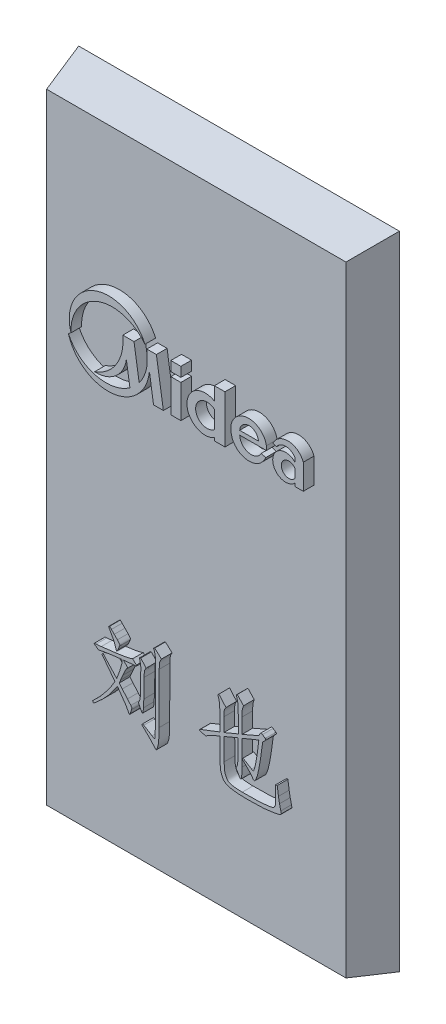
SolidWorks part; units mm, degrees
ref_plane "前视基准面" through (0, 0, 0) normal (0, 0, 1) x (1, 0, 0)
ref_plane "上视基准面" through (0, 0, 0) normal (0, 1, 0) x (1, 0, 0)
ref_plane "右视基准面" through (0, 0, 0) normal (1, 0, 0) x (0, 0, -1)
other "Configuration Table"
sketch "草图1" plane through (0, 0, 0) normal (0, 0, 1) x (1, 0, 0)
  line L18 (-15, -30) -> (15, -30)
  line L19 (-15, -30) -> (-15, 30)
  line L20 (-15, 30) -> (15, 30)
  line L21 (15, -30) -> (15, 30)
  line L22 (-15, -30) -> (15, 30) construction
  line L23 (-15, 30) -> (15, -30) construction
  point P0 (0, 0)
  dimension "D2" = 60
  dimension "D1" = 30
ref_plane "基准面1" through (0, 0, 4) normal (0, 0, 1) x (1, 0, 0)
sketch "草图2" plane through (0, 0, 4) normal (0, 0, 1) x (1, 0, 0)
  line L0 (-15, 30) -> (15, 30) construction
  line L1 (-14, -29) -> (14, -29)
  line L2 (-14, -29) -> (-14, 29)
  line L3 (-14, 29) -> (14, 29)
  line L4 (14, -29) -> (14, 29)
  line L5 (-14, -29) -> (14, 29) construction
  line L6 (-14, 29) -> (14, -29) construction
  line L7 (15, -30) -> (15, 30) construction
  point P0 (0, 0)
  dimension "D1" = 1
  dimension "D2" = 1
loft "放样1" add profiles "草图1", "草图2" connector at (-15, -30, 0) connector at (-14, -29, 4)
sketch "草图4" plane through (0, 0, 4) normal (0, 0, 1) x (1, 0, 0)
  line L6 (-14, -17) -> (14, -17) construction
  line L7 (-14, -29) -> (-14, 29) construction
  line L8 (14, -29) -> (14, 29) construction
  text T0 "刘也" font "汉仪长仿宋体" height 6
  dimension "D1" = 17
extrude "凸台-拉伸3" add sketch "草图4" along normal blind 1
sketch "草图5" plane through (0, 0, 0) normal (0, 0, -1) x (-1, 0, 0)
  line L4 (0, 18) -> (0, 0) construction
  line L5 (0, 0) -> (0, -18) construction
  line L6 (15, -30) -> (-15, -30) construction
  circle A7 centre (0, 0) radius 5.5
  circle A8 centre (0, 18) radius 5.5
  circle A9 centre (0, -18) radius 5.5
  dimension "D1" = 11
  dimension "D2" = 12
extrude "切除-拉伸1" cut sketch "草图5" against normal blind 2
sketch "草图7" plane through (0, 0, 4) normal (0, 0, 1) x (1, 0, 0)
  line L0 (3.2108, -13.9623) -> (1.3838, -14.6693) construction
  line L1 (1.3838, -14.8163) -> (1.8889, -14.9544) construction
  line L2 (3.2223, -14.2896) -> (3.2338, -16.284) construction
  line L3 (8.9065, -17.5088) -> (8.7864, -16.9911) construction
  line L4 (8.7864, -16.9911) -> (8.6892, -16.4387) construction
  line L5 (8.6892, -16.4387) -> (8.569, -15.6192) construction
  line L6 (8.569, -15.6192) -> (8.4258, -15.6358) construction
  line L7 (8.4258, -15.6358) -> (8.413, -17.2071) construction
  line L8 (3.6072, -16.1882) -> (3.5944, -14.1349) construction
  line L9 (3.5944, -14.1349) -> (4.9163, -13.5826) construction
  line L10 (4.9163, -13.5826) -> (4.9163, -14.7997) construction
  line L11 (4.832, -16.3186) -> (4.9892, -16.6024) construction
  line L12 (5.2654, -15.7918) -> (5.2654, -13.4445) construction
  line L13 (5.2654, -13.4445) -> (6.8507, -12.7976) construction
  line L14 (6.1782, -15.4901) -> (5.3728, -14.9979) construction
  line L15 (5.3728, -14.9979) -> (5.3012, -15.127) construction
  line L16 (5.3012, -15.127) -> (5.6131, -15.4211) construction
  line L17 (5.6131, -15.4211) -> (5.9737, -15.7918) construction
  line L18 (5.9737, -15.7918) -> (6.2984, -16.1971) construction
  line L19 (7.4401, -12.3744) -> (7.1882, -12.1839) construction
  line L20 (7.0195, -12.1583) -> (6.8277, -12.4524) construction
  line L21 (6.8277, -12.4524) -> (5.2769, -13.1249) construction
  line L22 (5.2769, -13.1249) -> (5.2769, -11.7185) construction
  line L23 (5.4214, -10.7341) -> (4.832, -10.1127) construction
  line L24 (4.832, -10.1127) -> (4.7361, -10.1997) construction
  line L25 (4.9291, -11.753) -> (4.9291, -13.2629) construction
  line L26 (4.9291, -13.2629) -> (3.5829, -13.8242) construction
  line L27 (3.5829, -13.8242) -> (3.5829, -12.547) construction
  line L28 (3.7746, -11.7006) -> (3.1149, -10.9412) construction
  line L29 (3.1149, -10.9412) -> (3.0178, -11.0447) construction
  line L30 (3.2108, -12.3744) -> (3.2108, -13.9623) construction
  line L31 (-2.8861, -10.2163) -> (-2.9948, -10.2853) construction
  line L32 (-2.8017, -11.5459) -> (-2.826, -16.4822) construction
  line L33 (-3.138, -17.4488) -> (-3.9076, -16.9744) construction
  line L34 (-3.9076, -16.9744) -> (-4.0035, -16.9054) construction
  line L35 (-4.0035, -16.9054) -> (-4.0994, -17.0089) construction
  line L36 (-4.0994, -17.0089) -> (-3.9677, -17.1547) construction
  line L37 (-3.9677, -17.1547) -> (-3.3553, -17.7505) construction
  line L38 (-3.3553, -17.7505) -> (-2.9219, -18.2248) construction
  line L39 (-2.4898, -16.4643) -> (-2.4655, -11.7185) construction
  line L40 (-2.2609, -10.7954) -> (-2.8861, -10.2163) construction
  line L41 (-4.1838, -12.4434) -> (-4.1953, -12.8142) construction
  line L42 (-4.1953, -12.8142) -> (-4.2323, -14.6437) construction
  line L43 (-4.3525, -15.5323) -> (-4.2554, -15.7138) construction
  line L44 (-4.2554, -15.7138) -> (-4.148, -15.9209) construction
  line L45 (-3.9434, -15.5847) -> (-3.9076, -14.8598) construction
  line L46 (-3.9076, -14.8598) -> (-3.8718, -13.0814) construction
  line L47 (-3.6915, -12.2453) -> (-4.1953, -11.675) construction
  line L48 (-4.1953, -11.675) -> (-4.3154, -11.7275) construction
  line L49 (-8.702, -17.3887) -> (-8.6061, -17.5344) construction
  line L50 (-8.6061, -17.5344) -> (-8.4731, -17.4309) construction
  line L51 (-5.5658, -16.215) -> (-5.4214, -16.4822) construction
  line L52 (-5.4214, -16.4822) -> (-5.3255, -16.6638) construction
  line L53 (-5.1695, -16.6638) -> (-5.0608, -16.2917) construction
  line L54 (-5.1209, -15.9734) -> (-5.4341, -15.6103) construction
  line L55 (-5.4341, -15.6103) -> (-5.9264, -15.049) construction
  line L56 (-5.9264, -15.049) -> (-6.214, -14.7128) construction
  line L57 (-6.214, -14.7128) -> (-6.0823, -14.411) construction
  line L58 (-6.0823, -14.411) -> (-5.8535, -13.8932) construction
  line L59 (-5.4098, -13.0993) -> (-5.7934, -12.6505) construction
  line L60 (-5.7934, -12.6505) -> (-5.1938, -12.5905) construction
  line L61 (-5.1938, -12.5905) -> (-4.6287, -12.547) construction
  line L62 (-4.5929, -12.4434) -> (-4.9649, -12.1238) construction
  line L63 (-7.885, -12.5905) -> (-8.3657, -12.625) construction
  line L64 (-8.4859, -12.7452) -> (-8.2328, -12.9356) construction
  line L65 (-8.2328, -12.9356) -> (-8.1612, -12.9957) construction
  line L66 (-8.1612, -12.9957) -> (-7.9566, -12.9523) construction
  line L67 (-7.9566, -12.9523) -> (-7.4516, -12.8577) construction
  line L68 (-7.4516, -12.8577) -> (-6.9722, -12.7886) construction
  line L69 (-6.9722, -12.7886) -> (-5.9506, -12.6672) construction
  line L70 (-5.9506, -12.6672) -> (-5.9506, -12.8577) construction
  line L71 (-7.6447, -13.1594) -> (-7.729, -13.0737) construction
  line L72 (-7.729, -13.0737) -> (-7.8249, -13.1773) construction
  line L73 (-7.8249, -13.1773) -> (-7.729, -13.3064) construction
  line L74 (-8.6176, -17.3017) -> (-8.702, -17.3887) construction
  line L75 (-7.2113, -10.6305) -> (-7.1154, -10.7775) construction
  line L76 (-6.9722, -11.0537) -> (-6.8034, -11.3554) construction
  line L77 (-6.5273, -12.0292) -> (-6.503, -12.1149) construction
  line L78 (-6.3112, -12.0292) -> (-6.191, -11.7185) construction
  line L79 (-6.3828, -11.2953) -> (-6.6717, -10.9936) construction
  line L80 (-6.6717, -10.9936) -> (-6.9351, -10.7264) construction
  line L81 (-6.9351, -10.7264) -> (-7.1039, -10.5538) construction
  line L82 (-7.1039, -10.5538) -> (-7.2113, -10.6305) construction
  line L83 (3.2108, -13.9623) -> (1.3838, -14.6693)
  line L84 (1.3838, -14.8163) -> (1.8889, -14.9544)
  line L85 (3.2223, -14.2896) -> (3.2338, -16.284)
  line L86 (8.9065, -17.5088) -> (8.7864, -16.9911)
  line L87 (8.7864, -16.9911) -> (8.6892, -16.4387)
  line L88 (8.6892, -16.4387) -> (8.569, -15.6192)
  line L89 (8.569, -15.6192) -> (8.4258, -15.6358)
  line L90 (8.4258, -15.6358) -> (8.413, -17.2071)
  line L91 (3.6072, -16.1882) -> (3.5944, -14.1349)
  line L92 (3.5944, -14.1349) -> (4.9163, -13.5826)
  line L93 (4.9163, -13.5826) -> (4.9163, -14.7997)
  line L94 (4.832, -16.3186) -> (4.9892, -16.6024)
  line L95 (5.2654, -15.7918) -> (5.2654, -13.4445)
  line L96 (5.2654, -13.4445) -> (6.8507, -12.7976)
  line L97 (6.1782, -15.4901) -> (5.3728, -14.9979)
  line L98 (5.3728, -14.9979) -> (5.3012, -15.127)
  line L99 (5.3012, -15.127) -> (5.6131, -15.4211)
  line L100 (5.6131, -15.4211) -> (5.9737, -15.7918)
  line L101 (5.9737, -15.7918) -> (6.2984, -16.1971)
  line L102 (7.4401, -12.3744) -> (7.1882, -12.1839)
  line L103 (7.0195, -12.1583) -> (6.8277, -12.4524)
  line L104 (6.8277, -12.4524) -> (5.2769, -13.1249)
  line L105 (5.2769, -13.1249) -> (5.2769, -11.7185)
  line L106 (5.4214, -10.7341) -> (4.832, -10.1127)
  line L107 (4.832, -10.1127) -> (4.7361, -10.1997)
  line L108 (4.9291, -11.753) -> (4.9291, -13.2629)
  line L109 (4.9291, -13.2629) -> (3.5829, -13.8242)
  line L110 (3.5829, -13.8242) -> (3.5829, -12.547)
  line L111 (3.7746, -11.7006) -> (3.1149, -10.9412)
  line L112 (3.1149, -10.9412) -> (3.0178, -11.0447)
  line L113 (3.2108, -12.3744) -> (3.2108, -13.9623)
  line L114 (-2.8861, -10.2163) -> (-2.9948, -10.2853)
  line L115 (-2.8017, -11.5459) -> (-2.826, -16.4822)
  line L116 (-3.138, -17.4488) -> (-3.9076, -16.9744)
  line L117 (-3.9076, -16.9744) -> (-4.0035, -16.9054)
  line L118 (-4.0035, -16.9054) -> (-4.0994, -17.0089)
  line L119 (-4.0994, -17.0089) -> (-3.9677, -17.1547)
  line L120 (-3.9677, -17.1547) -> (-3.3553, -17.7505)
  line L121 (-3.3553, -17.7505) -> (-2.9219, -18.2248)
  line L122 (-2.4898, -16.4643) -> (-2.4655, -11.7185)
  line L123 (-2.2609, -10.7954) -> (-2.8861, -10.2163)
  line L124 (-4.1838, -12.4434) -> (-4.1953, -12.8142)
  line L125 (-4.1953, -12.8142) -> (-4.2323, -14.6437)
  line L126 (-4.3525, -15.5323) -> (-4.2554, -15.7138)
  line L127 (-4.2554, -15.7138) -> (-4.148, -15.9209)
  line L128 (-3.9434, -15.5847) -> (-3.9076, -14.8598)
  line L129 (-3.9076, -14.8598) -> (-3.8718, -13.0814)
  line L130 (-3.6915, -12.2453) -> (-4.1953, -11.675)
  line L131 (-4.1953, -11.675) -> (-4.3154, -11.7275)
  line L132 (-8.702, -17.3887) -> (-8.6061, -17.5344)
  line L133 (-8.6061, -17.5344) -> (-8.4731, -17.4309)
  line L134 (-5.5658, -16.215) -> (-5.4214, -16.4822)
  line L135 (-5.4214, -16.4822) -> (-5.3255, -16.6638)
  line L136 (-5.1695, -16.6638) -> (-5.0608, -16.2917)
  line L137 (-5.1209, -15.9734) -> (-5.4341, -15.6103)
  line L138 (-5.4341, -15.6103) -> (-5.9264, -15.049)
  line L139 (-5.9264, -15.049) -> (-6.214, -14.7128)
  line L140 (-6.214, -14.7128) -> (-6.0823, -14.411)
  line L141 (-6.0823, -14.411) -> (-5.8535, -13.8932)
  line L142 (-5.4098, -13.0993) -> (-5.7934, -12.6505)
  line L143 (-5.7934, -12.6505) -> (-5.1938, -12.5905)
  line L144 (-5.1938, -12.5905) -> (-4.6287, -12.547)
  line L145 (-4.5929, -12.4434) -> (-4.9649, -12.1238)
  line L146 (-7.885, -12.5905) -> (-8.3657, -12.625)
  line L147 (-8.4859, -12.7452) -> (-8.2328, -12.9356)
  line L148 (-8.2328, -12.9356) -> (-8.1612, -12.9957)
  line L149 (-8.1612, -12.9957) -> (-7.9566, -12.9523)
  line L150 (-7.9566, -12.9523) -> (-7.4516, -12.8577)
  line L151 (-7.4516, -12.8577) -> (-6.9722, -12.7886)
  line L152 (-6.9722, -12.7886) -> (-5.9506, -12.6672)
  line L153 (-5.9506, -12.6672) -> (-5.9506, -12.8577)
  line L154 (-7.6447, -13.1594) -> (-7.729, -13.0737)
  line L155 (-7.729, -13.0737) -> (-7.8249, -13.1773)
  line L156 (-7.8249, -13.1773) -> (-7.729, -13.3064)
  line L157 (-8.6176, -17.3017) -> (-8.702, -17.3887)
  line L158 (-7.2113, -10.6305) -> (-7.1154, -10.7775)
  line L159 (-6.9722, -11.0537) -> (-6.8034, -11.3554)
  line L160 (-6.5273, -12.0292) -> (-6.503, -12.1149)
  line L161 (-6.3112, -12.0292) -> (-6.191, -11.7185)
  line L162 (-6.3828, -11.2953) -> (-6.6717, -10.9936)
  line L163 (-6.6717, -10.9936) -> (-6.9351, -10.7264)
  line L164 (-6.9351, -10.7264) -> (-7.1039, -10.5538)
  line L165 (-7.1039, -10.5538) -> (-7.2113, -10.6305)
  spline S0 degree 3 poles (-1033.717, 1696.6076) (14.5849, -31.3392) (2.3796, -13.84) (1.322, -14.7057) (1.3032, -14.7272) (1.2978, -14.7519) (1.3028, -14.776) (1.3219, -14.7941) (2.4833, -15.4174) (10.8456, 3.4261) (-689.6183, -1891.6231) knots -16.626684 -16.626684 -16.626684 -16.626684 0.172084 0.308952 0.423314 0.521848 0.615174 0.717267 0.839241 17.04599 17.04599 17.04599 17.04599 only from (1.3838, -14.6693) to (1.3838, -14.8163) construction
  spline S1 degree 3 poles (-1193.4267, 1588.4483) (4.6942, -35.4098) (-2.0793, -17.6856) (2.0886, -14.8069) (2.1786, -14.7467) (2.255, -14.7057) (2.3236, -14.6723) (2.394, -14.6406) (2.4842, -14.6016) (2.5935, -14.5536) (2.723, -14.4991) (2.8716, -14.4348) (21.1798, -6.8784) (36.675, 7.0863) (846.5091, -1827.4773) knots -9.913111 -9.913111 -9.913111 -9.913111 0.088354 0.168711 0.240996 0.305231 0.342298 0.393919 0.460114 0.539323 0.633116 0.74183 0.864014 40.342075 40.342075 40.342075 40.342075 only from (1.8889, -14.9544) to (3.2223, -14.2896) construction
  spline S2 degree 3 poles (-1996.6425, -26.0924) (21.1619, -1.4114) (2.9373, -9.1514) (3.2408, -16.6481) (3.2493, -16.8011) (3.2608, -16.9395) (3.287, -17.0743) (3.3282, -17.2177) (3.3889, -17.3745) (3.4475, -17.514) (3.5093, -17.6275) (3.5725, -17.7068) (3.6497, -17.778) (3.7401, -17.842) (3.8439, -17.8993) (3.961, -17.9489) (4.091, -17.9913) (4.2346, -18.0246) (4.3907, -18.0542) (4.5598, -18.0774) (4.7413, -18.0999) (4.9353, -18.1162) (5.1417, -18.1268) (5.3603, -18.1366) (17.0583, -18.3013) (28.6468, -3.9526) (45.2697, -2017.6338) knots -5.726077 -5.726077 -5.726077 -5.726077 0.051298 0.096629 0.136668 0.171139 0.205044 0.243843 0.287585 0.336355 0.362012 0.388335 0.415202 0.443856 0.474721 0.507699 0.543092 0.581467 0.622821 0.667242 0.714879 0.765695 0.819407 0.876414 0.936712 9.962298 9.962298 9.962298 9.962298 only from (3.2338, -16.284) to (5.8305, -18.1391) construction
  spline S3 degree 3 poles (-13.558, -2017.9262) (-16.1126, -3.2156) (-4.8916, -18.3162) (6.2967, -18.1363) (6.5077, -18.135) (6.702, -18.1289) (6.8797, -18.1244) (7.0413, -18.1179) (7.1862, -18.1106) (7.3593, -18.0983) (7.5693, -18.079) (7.8251, -18.0454) (8.0919, -18.0098) (8.3171, -17.9718) (8.4924, -17.939) (8.6085, -17.9125) (8.7077, -17.8849) (8.7894, -17.8553) (8.8564, -17.8272) (8.9046, -17.795) (9.7801, -17.0547) (-10.3073, -3.2872) (1708.116, -1071.7951) knots -10.275083 -10.275083 -10.275083 -10.275083 0.076298 0.147407 0.213324 0.274064 0.329613 0.379985 0.425587 0.465631 0.542665 0.62318 0.707468 0.794943 0.837249 0.874555 0.906545 0.933712 0.95606 0.97423 0.988354 1.993762 1.993762 1.993762 1.993762 only from (5.8305, -18.1391) to (8.9538, -17.7249) construction
  spline S4 degree 3 poles (1950.4824, 462.1548) (-3.6389, -24.2841) (9.4886, -19.2587) (8.928, -17.6283) (8.3828, -15.5017) (24.8318, -10.629) (-1966.0478, -332.6785) knots -22.527171 -22.527171 -22.527171 -22.527171 0.152758 0.441236 0.761695 29.779876 29.779876 29.779876 29.779876 only from (8.9538, -17.7249) to (8.9065, -17.5088) construction
  spline S5 degree 3 poles (1964.363, -433.7342) (-12.5579, -7.9686) (9.2006, -15.0961) (8.374, -17.3632) (8.3303, -17.4427) (8.2869, -17.5147) (8.228, -17.5691) (8.157, -17.6037) (8.0635, -17.637) (7.9458, -17.6647) (7.8043, -17.6919) (7.6382, -17.714) (7.4476, -17.7331) (7.1586, -17.7525) (6.7742, -17.7729) (6.2972, -17.7876) (-12.0936, -18.089) (-30.4237, 1.2715) (-38.3924, -2017.04) knots -2.060584 -2.060584 -2.060584 -2.060584 0.022746 0.046909 0.073942 0.103777 0.121266 0.144564 0.173661 0.209707 0.252274 0.302159 0.35908 0.423101 0.560508 0.702361 0.848718 16.964876 16.964876 16.964876 16.964876 only from (8.413, -17.2071) to (5.3012, -17.7939) construction
  spline S6 degree 3 poles (-46.7827, -2016.9641) (22.8077, 5.2469) (13.3561, -18.3583) (4.7621, -17.7744) (4.5344, -17.7516) (4.3394, -17.7124) (4.1743, -17.6679) (4.0418, -17.6087) (3.9373, -17.5417) (3.8494, -17.4317) (3.7799, -17.2879) (3.7089, -17.1204) (3.6584, -16.9548) (3.628, -16.7397) (3.0291, -6.34) (22.0683, 4.4844) (-1996.1462, -34.556) knots -8.866171 -8.866171 -8.866171 -8.866171 0.102703 0.194721 0.275299 0.345385 0.405658 0.456275 0.49919 0.535795 0.603996 0.668093 0.728927 0.787086 0.898182 11.780137 11.780137 11.780137 11.780137 only from (5.3012, -17.7939) to (3.6072, -16.1882) construction
  spline S7 degree 3 poles (2004.3322, 28.2132) (-5.4357, 8.8885) (4.9939, -3.0766) (4.9157, -15.1159) (4.913, -15.2229) (4.9105, -15.3009) (4.9062, -15.3675) (4.8976, -15.4411) (4.8881, -15.5311) (4.8742, -15.6326) (4.8595, -15.7344) (4.8403, -15.8267) (4.8184, -15.904) (4.7924, -15.9663) (4.7664, -16.0149) (4.7485, -16.0553) (4.7377, -16.0864) (4.7267, -16.1124) (4.7369, -16.1442) (4.7545, -16.1874) (8.4419, -22.4311) (7.4888, -21.5343) (1094.0182, -1693.6924) knots -22.721442 -22.721442 -22.721442 -22.721442 0.117235 0.209236 0.277643 0.321637 0.358354 0.405016 0.463185 0.53135 0.600551 0.659631 0.71141 0.753745 0.788334 0.81677 0.837638 0.852065 0.86867 0.898605 0.942334 14.623876 14.623876 14.623876 14.623876 only from (4.9163, -14.7997) to (4.832, -16.3186) construction
  spline S8 degree 3 poles (-1550.7197, -1273.4139) (19.3456, 2.9931) (3.2309, -14.1918) (5.0799, -16.7505) (5.7712, -17.6613) (19.4263, 1.9782) (-1061.0354, -1708.7198) knots -34.275912 -34.275912 -34.275912 -34.275912 0.381659 0.667499 0.869536 12.383747 12.383747 12.383747 12.383747 only from (4.9892, -16.6024) to (5.1567, -16.8095) construction
  spline S9 degree 3 poles (918.7555, -1795.635) (-5.5243, 1.4675) (4.8071, -17.3305) (5.1958, -16.7827) (5.2129, -16.7483) (5.2282, -16.7063) (5.2394, -16.6557) (5.2459, -16.5944) (5.2522, -16.5121) (5.257, -16.4089) (5.2608, -16.2845) (5.2627, -16.1391) (5.4392, -7.5851) (-9.7444, 1.0472) (2005.1553, -7.1429) knots -1.687714 -1.687714 -1.687714 -1.687714 0.017456 0.042472 0.079552 0.130072 0.168818 0.227795 0.306061 0.404936 0.523255 0.662264 0.820778 24.999128 24.999128 24.999128 24.999128 only from (5.1567, -16.8095) to (5.2654, -15.7918) construction
  spline S10 degree 3 poles (1999.4433, -182.4933) (-0.9536, 17.1275) (8.3501, 1.4035) (6.8086, -13.2123) (6.7917, -13.371) (6.7732, -13.5025) (6.7549, -13.6268) (6.7362, -13.7638) (6.7125, -13.9226) (6.6791, -14.1669) (6.6279, -14.4944) (6.5596, -14.8224) (6.5056, -15.0718) (6.4665, -15.2245) (6.4351, -15.3421) (6.405, -15.4266) (6.3778, -15.4844) (6.3562, -15.5253) (6.3378, -15.5519) (6.3166, -15.5656) (6.2921, -15.5599) (6.2639, -15.5443) (4.0424, -14.2877) (11.2127, 0.4883) (-1139.8748, -1654.3969) knots -14.529546 -14.529546 -14.529546 -14.529546 0.077669 0.143357 0.196643 0.237586 0.276416 0.322552 0.376056 0.437289 0.569617 0.708128 0.772877 0.82528 0.866104 0.894742 0.914992 0.930089 0.941025 0.94733 0.953792 0.964678 0.979985 3.500837 3.500837 3.500837 3.500837 only from (6.8507, -12.7976) to (6.1782, -15.4901) construction
  spline S11 degree 3 poles (-1459.7871, -1376.4789) (16.124, -1.0165) (4.8212, -14.6345) (6.361, -16.2729) (7.1105, -16.8641) (15.6434, 1.6427) (-747.2579, -1868.7131) knots -40.720986 -40.720986 -40.720986 -40.720986 0.346655 0.629517 0.83833 17.401909 17.401909 17.401909 17.401909 only from (6.2984, -16.1971) to (6.4186, -16.3007) construction
  spline S12 degree 3 poles (837.9651, -1835.1249) (-8.1419, 10.6055) (5.776, -17.2113) (6.5025, -16.2565) (6.528, -16.2095) (6.5563, -16.1512) (6.5901, -16.0734) (6.631, -15.9775) (6.6736, -15.8661) (6.7146, -15.7421) (6.7515, -15.6071) (6.7856, -15.4601) (6.8204, -15.2999) (6.8542, -15.124) (6.8917, -14.9328) (6.9306, -14.7215) (6.9732, -14.4828) (7.0122, -14.2083) (7.0571, -13.8958) (7.0902, -13.6158) (7.1179, -13.389) (7.1385, -13.2361) (7.1567, -13.1048) (7.1715, -12.9952) (7.1853, -12.9069) (7.1977, -12.8407) (7.2081, -12.7966) (7.217, -12.763) (7.2413, -12.7362) (7.2737, -12.7029) (7.3166, -12.6607) (7.3686, -12.617) (7.4169, -12.5708) (7.4586, -12.5329) (7.4821, -12.4989) (7.4993, -12.4634) (7.0362, -10.9223) (-17.6107, -31.0912) (1493.2118, 1326.3414) knots -0.749252 -0.749252 -0.749252 -0.749252 0.011116 0.024256 0.034759 0.050015 0.070334 0.09545 0.124469 0.15558 0.188759 0.224443 0.263394 0.305925 0.352459 0.40264 0.459525 0.525733 0.60077 0.685168 0.727217 0.76409 0.795449 0.821898 0.843179 0.859308 0.869947 0.875726 0.883767 0.895184 0.909185 0.926664 0.943691 0.957044 0.966676 0.973237 0.984469 2.007557 2.007557 2.007557 2.007557 only from (6.4186, -16.3007) to (7.4401, -12.3744) construction
  spline S13 degree 3 poles (902.0496, 1776.4099) (0.6886, -34.6242) (9.0767, -12.9356) (7.086, -12.1281) (6.1315, -12.1467) (19.65, -37.5566) (-984.4161, 1724.6464) knots -32.736634 -32.736634 -32.736634 -32.736634 0.367152 0.634154 0.821366 13.935133 13.935133 13.935133 13.935133 only from (7.1882, -12.1839) to (7.0195, -12.1583) construction
  spline S14 degree 3 poles (-1994.6009, 0.495) (23.7054, -26.4113) (4.9761, -18.7485) (5.2835, -11.3643) (5.2914, -11.232) (5.3038, -11.1262) (5.3257, -11.034) (5.3512, -10.9406) (6.9792, -5.8121) (22.7426, -5.6507) (-1877.5534, 663.1337) knots -21.608795 -21.608795 -21.608795 -21.608795 0.198899 0.364768 0.496393 0.59539 0.682927 0.77943 0.885076 16.774062 16.774062 16.774062 16.774062 only from (5.2769, -11.7185) to (5.4214, -10.7341) construction
  spline S15 degree 3 poles (1902.8334, 619.7227) (-16.1551, -6.6372) (3.4236, -5.5784) (4.816, -10.4468) (4.8463, -10.5591) (4.8758, -10.7012) (4.902, -10.8854) (4.9158, -11.0799) (4.9214, -11.254) (4.9279, -11.4048) (4.905, -22.6176) (16.3078, -33.5295) (-1993.4919, -88.7053) knots -9.399112 -9.399112 -9.399112 -9.399112 0.086759 0.167144 0.240968 0.308143 0.443474 0.594867 0.67934 0.775169 0.882309 22.030604 22.030604 22.030604 22.030604 only from (4.7361, -10.1997) to (4.9291, -11.753) construction
  spline S16 degree 3 poles (-1996.3066, -6.3279) (21.0986, -26.1786) (3.2376, -19.0978) (3.5925, -12.2086) (3.6071, -12.0674) (3.6279, -11.9648) (3.6579, -11.8939) (3.6875, -11.8361) (6.3076, -7.6291) (19.1276, -10.4641) (-1635.6374, 1133.6983) knots -22.753125 -22.753125 -22.753125 -22.753125 0.200316 0.389353 0.554689 0.680516 0.74126 0.814082 0.900083 17.48624 17.48624 17.48624 17.48624 only from (3.5829, -12.547) to (3.7746, -11.7006) construction
  spline S17 degree 3 poles (1903.9912, 610.2623) (-20.7158, -5.6325) (1.4769, -5.2348) (3.1267, -11.4022) (3.1599, -11.5753) (3.1876, -11.7958) (3.8456, -21.4883) (-18.235, -31.7664) (2002.9406, 15.7492) knots -13.754831 -13.754831 -13.754831 -13.754831 0.142454 0.27858 0.408689 0.533703 0.771853 21.965234 21.965234 21.965234 21.965234 only from (3.0178, -11.0447) to (3.2108, -12.3744) construction
  spline S18 degree 3 poles (1863.0803, 709.0915) (-22.3797, -4.1401) (-5.0305, -4.4694) (-2.8997, -10.5404) (-2.8683, -10.6465) (-2.844, -10.7698) (-2.829, -10.9212) (-2.8225, -11.0733) (-2.8168, -11.193) (-2.8154, -11.2703) (-2.8106, -11.3328) (-2.8079, -11.3968) (-2.5223, -14.669) (-19.2275, -18.627) (1995.8178, 61.3832) knots -14.7087 -14.7087 -14.7087 -14.7087 0.116167 0.216181 0.30306 0.374052 0.509134 0.657525 0.72919 0.788892 0.837713 0.875556 0.938334 8.497053 8.497053 8.497053 8.497053 only from (-2.9948, -10.2853) to (-2.8017, -11.5459) construction
  spline S19 degree 3 poles (1996.6884, -57.1725) (-15.54, -4.2723) (-2.5643, -10.6635) (-2.8326, -16.6987) (-2.8349, -16.7929) (-2.8368, -16.8769) (-2.8416, -16.9497) (-2.8431, -17.0124) (-2.8477, -17.0639) (-2.8518, -17.1377) (-2.8594, -17.2275) (-2.8586, -17.3285) (-2.6706, -19.1698) (-24.0229, -19.8512) (1993.9836, -127.1361) knots -18.086944 -18.086944 -18.086944 -18.086944 0.116901 0.223456 0.319585 0.404033 0.479451 0.541837 0.595221 0.636857 0.766948 0.869544 0.944906 6.362298 6.362298 6.362298 6.362298 only from (-2.826, -16.4822) to (-2.8618, -17.4654) construction
  spline S20 degree 3 poles (1920.7346, -564.8783) (-19.9028, -9.0246) (-2.2232, -15.9139) (-2.8844, -17.541) (-2.8944, -17.5636) (-2.9124, -17.5786) (-2.943, -17.5624) (-2.9871, -17.5419) (-7.9881, -14.4729) (-0.924, -15.4233) (-1899.5268, 617.8288) knots -13.418067 -13.418067 -13.418067 -13.418067 0.123946 0.216991 0.278308 0.31908 0.381479 0.515917 0.721003 45.525651 45.525651 45.525651 45.525651 only from (-2.8618, -17.4654) to (-3.138, -17.4488) construction
  spline S21 degree 3 poles (194.9213, -2008.3902) (-15.0275, 1.5883) (-8.4676, -12.6222) (-2.8057, -18.3428) (-2.0182, -19.0945) (7.0662, -6.6445) (-1066.911, -1711.4586) knots -97.933846 -97.933846 -97.933846 -97.933846 0.408799 0.710783 0.906834 13.513962 13.513962 13.513962 13.513962 only from (-2.9219, -18.2248) to (-2.7416, -18.3897) construction
  spline S22 degree 3 poles (1541.3019, -1289.3663) (-17.2182, -8.6749) (-3.0151, -19.2135) (-2.6957, -18.315) (-2.6594, -18.2339) (-2.6181, -18.1202) (-2.5776, -17.9866) (-2.5431, -17.8417) (-2.5239, -17.6904) (-2.5098, -17.4826) (-2.5022, -17.2234) (-2.497, -16.9689) (-2.4939, -16.7788) (-2.491, -16.6565) (-2.4063, -10.64) (-11.8864, -4.6267) (1997.4337, -6.5983) knots -1.306783 -1.306783 -1.306783 -1.306783 0.011073 0.038994 0.08476 0.148534 0.222584 0.297979 0.375406 0.454948 0.615659 0.771094 0.84328 0.905715 0.957736 10.02345 10.02345 10.02345 10.02345 only from (-2.7416, -18.3897) to (-2.4898, -16.4643) construction
  spline S23 degree 3 poles (-2002.0433, 23.4082) (17.2178, -26.8655) (-2.9385, -18.8244) (-2.4518, -11.3454) (-2.4395, -11.2317) (-2.4299, -11.1629) (-2.4183, -11.1079) (-2.4062, -11.0612) (-2.3851, -11.014) (-2.3537, -10.9557) (0.2121, -6.3458) (14.755, -8.7652) (-1720.7414, 1012.1287) knots -22.788299 -22.788299 -22.788299 -22.788299 0.226747 0.424712 0.510059 0.582424 0.640662 0.684729 0.732249 0.801029 0.890645 17.139984 17.139984 17.139984 17.139984 only from (-2.4655, -11.7185) to (-2.2609, -10.7954) construction
  spline S24 degree 3 poles (1924.5555, 516.4873) (-21.4595, -4.1063) (-5.6484, -6.1098) (-4.2553, -11.9618) (-4.2351, -12.066) (-4.2157, -12.1849) (-3.2666, -19.1695) (-14.338, -27.5253) (1984.5585, 198.7689) knots -24.265145 -24.265145 -24.265145 -24.265145 0.176124 0.336499 0.483023 0.612769 0.832275 29.485687 29.485687 29.485687 29.485687 only from (-4.3154, -11.7275) to (-4.1838, -12.4434) construction
  spline S25 degree 3 poles (1993.4071, -111.1275) (-26.4009, -2.323) (-3.6574, -9.2924) (-4.2529, -14.9872) (-4.2827, -15.1305) (-4.3269, -15.2317) (-4.3657, -15.2981) (-4.3838, -15.3404) (-4.396, -15.3739) (-4.4028, -15.4128) (-3.7015, -17.7808) (17.82, -6.713) (-1681.3534, -1105.1804) knots -18.0051 -18.0051 -18.0051 -18.0051 0.201752 0.379581 0.534025 0.67384 0.735013 0.783251 0.822556 0.850486 0.909807 8.568288 8.568288 8.568288 8.568288 only from (-4.2323, -14.6437) to (-4.3525, -15.5323) construction
  spline S26 degree 3 poles (-1512.9602, -1328.6343) (10.4966, 3.2816) (-5.5522, -14.0466) (-4.0797, -16.0348) (-4.0465, -16.064) (-4.0156, -16.055) (-4.0025, -16.0314) (-3.9917, -16.0026) (-3.9815, -15.9618) (-3.9734, -15.9091) (-3.9642, -15.8448) (-3.9571, -15.7684) (-3.4918, -10.72) (-16.7031, -4.6524) (1991.2791, -152.9923) knots -10.887367 -10.887367 -10.887367 -10.887367 0.121964 0.207693 0.260892 0.300142 0.329863 0.376288 0.436469 0.514652 0.611416 0.722891 0.853081 22.971798 22.971798 22.971798 22.971798 only from (-4.148, -15.9209) to (-3.9434, -15.5847) construction
  spline S27 degree 3 poles (1994.0865, -101.0049) (-13.6723, -29.9635) (-3.8891, -21.5767) (-3.8702, -12.858) (-3.866, -12.7715) (-3.86, -12.6843) (-3.8474, -12.597) (-3.8347, -12.516) (-3.8137, -12.4521) (-3.7836, -12.3943) (-1.8693, -9.0083) (15.3369, -14.8877) (-1709.4277, 1031.8458) knots -29.538415 -29.538415 -29.538415 -29.538415 0.141799 0.263135 0.361172 0.438866 0.562703 0.663904 0.719374 0.792594 0.886876 14.061788 14.061788 14.061788 14.061788 only from (-3.8718, -13.0814) to (-3.6915, -12.2453) construction
  spline S28 degree 3 poles (1264.9967, -1559.4891) (-31.5873, -12.0786) (-13.6284, -22.0641) (-8.1342, -17.1422) (-7.9369, -16.9598) (-7.7283, -16.7545) (-7.5206, -16.5461) (-7.3343, -16.3462) (-7.1732, -16.1672) (-7.0581, -16.0237) (-6.9736, -15.91) (-6.9052, -15.8183) (-6.8336, -15.7144) (-6.7531, -15.6022) (-6.67, -15.4779) (-6.5781, -15.3451) (2.1562, -2.044) (17.435, 6.7071) (-1628.834, 1154.0726) knots -6.726074 -6.726074 -6.726074 -6.726074 0.062764 0.136145 0.220514 0.315903 0.411855 0.497633 0.57328 0.638674 0.670791 0.706683 0.746446 0.789663 0.836764 0.887318 0.941766 15.825984 15.825984 15.825984 15.825984 only from (-8.4731, -17.4309) to (-6.3828, -15.049) construction
  spline S29 degree 3 poles (-1774.7239, -949.3367) (-0.7487, -7.6484) (-7.3553, -13.3952) (-6.347, -15.1129) (-6.313, -15.1624) (-6.2693, -15.2266) (-6.2164, -15.3059) (-6.1504, -15.3976) (-6.0752, -15.5038) (-5.9929, -15.6196) (-5.909, -15.7352) (-5.8309, -15.8422) (-5.7637, -15.9368) (-5.7051, -16.0177) (-5.6581, -16.0866) (-5.617, -16.1403) (-2.5499, -20.6038) (-3.1453, -27.2731) (1710.5712, 1010.7307) knots -4.10249 -4.10249 -4.10249 -4.10249 0.017268 0.047445 0.089524 0.143804 0.211032 0.29024 0.381658 0.485286 0.589437 0.682632 0.764344 0.833847 0.893123 0.939986 0.976096 12.299151 12.299151 12.299151 12.299151 only from (-6.3828, -15.049) to (-5.5658, -16.215) construction
  spline S30 degree 3 poles (-1652.1034, -1151.5707) (8.8374, -2.9824) (-6.3284, -15.4657) (-5.2823, -16.7295) (-5.2616, -16.749) (-5.239, -16.7551) (-5.2169, -16.7491) (-5.1987, -16.7299) (-4.4002, -15.3061) (-20.3074, -6.3517) (1819.6509, -834.9933) knots -19.315907 -19.315907 -19.315907 -19.315907 0.184014 0.329932 0.435758 0.52042 0.60011 0.698183 0.82936 20.217518 20.217518 20.217518 20.217518 only from (-5.3255, -16.6638) to (-5.1695, -16.6638) construction
  spline S31 degree 3 poles (1756.3388, -963.5015) (-15.7851, -19.7388) (-6.0338, -20.2901) (-5.0347, -16.1894) (-5.0317, -16.153) (-5.0297, -16.1236) (-5.0402, -16.096) (-5.057, -16.0623) (-7.8026, -12.1779) (-16.0197, -15.5805) (1187.0566, 1589.806) knots -35.897109 -35.897109 -35.897109 -35.897109 0.175028 0.3144 0.421741 0.491694 0.565052 0.672076 0.818098 41.504706 41.504706 41.504706 41.504706 only from (-5.0608, -16.2917) to (-5.1209, -15.9734) construction
  spline S32 degree 3 poles (-1844.512, 772.8216) (-1.9985, -31.3954) (-8.803, -20.3942) (-5.7663, -13.6971) (-5.7298, -13.6114) (-5.6969, -13.5363) (-5.6669, -13.4717) (-5.6414, -13.4167) (-5.62, -13.3716) (-5.5873, -13.3017) (-3.5534, -10.1993) (22.2359, -28.7518) (-1476.7841, 1341.5083) knots -23.688236 -23.688236 -23.688236 -23.688236 0.124711 0.237544 0.339212 0.428998 0.50564 0.571681 0.627122 0.668853 0.823736 12.607364 12.607364 12.607364 12.607364 only from (-5.8535, -13.8932) to (-5.4098, -13.0993) construction
  spline S33 degree 3 poles (1048.4675, -1712.7468) (-20.15, 9.6222) (-5.0308, -13.2656) (-4.5787, -12.5119) (-4.4352, -11.4786) (-31.1321, -16.4036) (1947.3773, 423.0108) knots -17.330031 -17.330031 -17.330031 -17.330031 0.228603 0.460739 0.719052 22.488112 22.488112 22.488112 22.488112 only from (-4.6287, -12.547) to (-4.5929, -12.4434) construction
  spline S34 degree 3 poles (617.1539, -1912.8033) (1.0615, 6.6518) (0.4277, -10.6214) (-5.2524, -12.2113) (-5.4248, -12.2495) (-5.6173, -12.2898) (-5.8305, -12.3277) (-6.0647, -12.3642) (-16.7545, -13.9589) (-29.7673, 2.3999) (227.2617, -1998.576) knots -10.40378 -10.40378 -10.40378 -10.40378 0.082838 0.177515 0.284544 0.402898 0.534005 0.677173 0.832565 20.129151 20.129151 20.129151 20.129151 only from (-4.9649, -12.1238) to (-6.5873, -12.4345) construction
  spline S35 degree 3 poles (298.0282, -1988.6784) (34.5431, 3.4816) (14.3568, -9.9504) (-7.256, -12.5157) (-26.2506, -14.8362) (-46.4544, -6.0355) (171.7781, -2004.1497) knots -49.192308 -49.192308 -49.192308 -49.192308 0.264132 0.518317 0.763645 44.186385 44.186385 44.186385 44.186385 only from (-6.5873, -12.4345) to (-7.885, -12.5905) construction
  spline S36 degree 3 poles (-1461.4057, 1361.6465) (11.9395, -25.8139) (-5.9466, -12.0262) (-8.5083, -12.6493) (-8.5576, -12.6619) (-8.5585, -12.6948) (-6.6522, -14.1057) (-12.4698, 0.822) (848.919, -1819.5851) knots -27.163084 -27.163084 -27.163084 -27.163084 0.274008 0.539418 0.638409 0.701183 0.813539 22.170768 22.170768 22.170768 22.170768 only from (-8.3657, -12.625) to (-8.4859, -12.7452) construction
  spline S37 degree 3 poles (1980.3886, -245.9002) (-25.6618, -4.0136) (-5.2924, -9.814) (-5.9842, -13.0963) (-6.0243, -13.2582) (-6.0787, -13.4503) (-6.1499, -13.6689) (-6.2318, -13.9123) (-11.99, -28.9406) (-30.0035, -38.8194) (1823.522, -820.849) knots -5.750981 -5.750981 -5.750981 -5.750981 0.058152 0.137295 0.236273 0.356767 0.494511 0.647688 0.816423 29.295179 29.295179 29.295179 29.295179 only from (-5.9506, -12.8577) to (-6.4429, -14.4545) construction
  spline S38 degree 3 poles (-1440.4806, -1408.4344) (12.2022, -13.7825) (-2.3288, -18.9321) (-6.635, -14.2521) (-6.7478, -14.1367) (-6.9051, -13.9638) (-7.1046, -13.7457) (-7.3024, -13.5363) (-7.4406, -13.3794) (-7.5273, -13.2883) (-11.1426, -9.2579) (-21.1289, -11.1301) (1455.1445, 1350.6897) knots -10.550678 -10.550678 -10.550678 -10.550678 0.072662 0.155077 0.246174 0.346541 0.551898 0.74801 0.835624 0.906789 0.961595 10.027963 10.027963 10.027963 10.027963 only from (-6.4429, -14.4545) to (-7.6447, -13.1594) construction
  spline S39 degree 3 poles (-1690.9874, -1093.1833) (3.3964, -3.003) (-8.5702, -12.3185) (-7.6792, -13.3782) (-7.6356, -13.4372) (-7.5827, -13.4978) (-7.5262, -13.5706) (-7.4574, -13.6543) (-7.3699, -13.7703) (-7.2605, -13.9156) (-7.1281, -14.0897) (-6.975, -14.2939) (4.9528, -30.4112) (25.9086, -39.6948) (-1573.915, -1256.6215) knots -2.148203 -2.148203 -2.148203 -2.148203 0.015763 0.043388 0.082758 0.134752 0.173579 0.232037 0.310356 0.408975 0.526794 0.664916 0.822376 33.019448 33.019448 33.019448 33.019448 only from (-7.729, -13.3064) to (-6.6116, -14.7818) construction
  spline S40 degree 3 poles (1720.3243, -1023.3234) (-16.1487, 18.5257) (-0.3829, -5.2401) (-7.063, -15.5177) (-7.2989, -15.8542) (-7.5036, -16.115) (-7.6664, -16.3087) (-7.7781, -16.444) (-7.8861, -16.5659) (-7.9856, -16.679) (-8.079, -16.7812) (-8.1654, -16.8734) (-8.2462, -16.9542) (-8.3206, -17.0243) (-8.3868, -17.0855) (-8.4452, -17.1383) (-8.4946, -17.184) (-8.5356, -17.2221) (-8.5675, -17.2534) (-8.5919, -17.2758) (-10.0031, -18.7121) (-13.9652, -17.5077) (1380.8721, -1455.6115) knots -10.967114 -10.967114 -10.967114 -10.967114 0.13677 0.268528 0.395276 0.51773 0.575816 0.629956 0.680367 0.726837 0.769636 0.808773 0.843982 0.87557 0.903536 0.927593 0.948568 0.965902 0.979597 0.98994 0.996647 2.846485 2.846485 2.846485 2.846485 only from (-6.6116, -14.7818) to (-8.6176, -17.3017) construction
  spline S41 degree 3 poles (-1863.6245, -754.3794) (4.4911, -3.082) (-7.7846, -9.5752) (-7.0741, -10.8691) (-4.3579, -16.0121) (12.1418, -14.6441) (-1809.0679, -878.3222) knots -13.550654 -13.550654 -13.550654 -13.550654 0.090846 0.287239 0.590215 56.191237 56.191237 56.191237 56.191237 only from (-7.1154, -10.7775) to (-6.9722, -11.0537) construction
  spline S42 degree 3 poles (1834.9168, 768.1255) (-43.4567, -10.4562) (24.5419, 1.0806) (-32.1871, -38.5399) (1852.1265, 726.1252) knots -30.614491 -30.614491 -30.614491 -30.614491 0.497436 31.719294 31.719294 31.719294 31.719294 only from (-6.8034, -11.3554) to (-6.5273, -12.0292) construction
  spline S43 degree 3 poles (-1865.1417, -750.4644) (10.0329, -1.5337) (-7.3015, -10.4965) (-6.4726, -12.1947) (-6.45, -12.2151) (-6.4207, -12.2124) (-6.395, -12.1889) (-6.3692, -12.1506) (-4.9295, -9.4946) (-20.1862, 0.6082) (1823.1195, -820.1308) knots -15.623058 -15.623058 -15.623058 -15.623058 0.147979 0.251119 0.323111 0.388004 0.477994 0.606878 0.779247 25.920813 25.920813 25.920813 25.920813 only from (-6.503, -12.1149) to (-6.3112, -12.0292) construction
  spline S44 degree 3 poles (-1912.8987, -615.0411) (10.2854, -11.3835) (-7.4086, -14.4578) (-6.1458, -11.6023) (-6.1514, -11.5735) (-6.1633, -11.5549) (-6.1798, -11.5283) (-6.2061, -11.4958) (-6.2388, -11.4549) (-6.28, -11.4078) (-12.3004, -4.7951) (-23.0878, -2.3486) (1486.2203, 1319.7709) knots -17.033327 -17.033327 -17.033327 -17.033327 0.164438 0.264555 0.289914 0.332187 0.391502 0.47307 0.575597 0.69724 0.838081 52.760377 52.760377 52.760377 52.760377 only from (-6.191, -11.7185) to (-6.3828, -11.2953) construction
  spline S45 degree 3 poles (1.3838, -14.6693) (1.3711, -14.6746) (1.3482, -14.6842) (1.322, -14.7057) (1.3032, -14.7272) (1.2978, -14.7519) (1.3028, -14.776) (1.3219, -14.7941) (1.3491, -14.8087) (1.3713, -14.8135) (1.3838, -14.8163) knots 0 0 0 0 0.172084 0.308952 0.423314 0.521848 0.615174 0.717267 0.839241 1 1 1 1
  spline S46 degree 3 poles (1.8889, -14.9544) (1.9235, -14.9272) (1.9897, -14.8752) (2.0886, -14.8069) (2.1786, -14.7467) (2.255, -14.7057) (2.3236, -14.6723) (2.394, -14.6406) (2.4842, -14.6016) (2.5935, -14.5536) (2.723, -14.4991) (2.8716, -14.4348) (3.0408, -14.365) (3.1597, -14.3156) (3.2223, -14.2896) knots 0 0 0 0 0.088354 0.168711 0.240996 0.305231 0.342298 0.393919 0.460114 0.539323 0.633116 0.74183 0.864014 1 1 1 1
  spline S47 degree 3 poles (3.2338, -16.284) (3.2338, -16.3497) (3.2337, -16.4733) (3.2408, -16.6481) (3.2493, -16.8011) (3.2608, -16.9395) (3.287, -17.0743) (3.3282, -17.2177) (3.3889, -17.3745) (3.4475, -17.514) (3.5093, -17.6275) (3.5725, -17.7068) (3.6497, -17.778) (3.7401, -17.842) (3.8439, -17.8993) (3.961, -17.9489) (4.091, -17.9913) (4.2346, -18.0246) (4.3907, -18.0542) (4.5598, -18.0774) (4.7413, -18.0999) (4.9353, -18.1162) (5.1417, -18.1268) (5.3603, -18.1366) (5.5914, -18.1398) (5.7495, -18.1394) (5.8305, -18.1391) knots 0 0 0 0 0.051298 0.096629 0.136668 0.171139 0.205044 0.243843 0.287585 0.336355 0.362012 0.388335 0.415202 0.443856 0.474721 0.507699 0.543092 0.581467 0.622821 0.667242 0.714879 0.765695 0.819407 0.876414 0.936712 1 1 1 1
  spline S48 degree 3 poles (5.8305, -18.1391) (5.9119, -18.1394) (6.0691, -18.1399) (6.2967, -18.1363) (6.5077, -18.135) (6.702, -18.1289) (6.8797, -18.1244) (7.0413, -18.1179) (7.1862, -18.1106) (7.3593, -18.0983) (7.5693, -18.079) (7.8251, -18.0454) (8.0919, -18.0098) (8.3171, -17.9718) (8.4924, -17.939) (8.6085, -17.9125) (8.7077, -17.8849) (8.7894, -17.8553) (8.8564, -17.8272) (8.9046, -17.795) (8.9417, -17.7637) (8.9501, -17.737) (8.9538, -17.7249) knots 0 0 0 0 0.076298 0.147407 0.213324 0.274064 0.329613 0.379985 0.425587 0.465631 0.542665 0.62318 0.707468 0.794943 0.837249 0.874555 0.906545 0.933712 0.95606 0.97423 0.988354 1 1 1 1
  spline S49 degree 3 poles (8.9538, -17.7249) (8.9519, -17.7138) (8.9463, -17.6816) (8.928, -17.6283) (8.9124, -17.5675) (8.9083, -17.5264) (8.9065, -17.5088) knots 0 0 0 0 0.152758 0.441236 0.761695 1 1 1 1
  spline S50 degree 3 poles (8.413, -17.2071) (8.4097, -17.2325) (8.4027, -17.2847) (8.374, -17.3632) (8.3303, -17.4427) (8.2869, -17.5147) (8.228, -17.5691) (8.157, -17.6037) (8.0635, -17.637) (7.9458, -17.6647) (7.8043, -17.6919) (7.6382, -17.714) (7.4476, -17.7331) (7.1586, -17.7525) (6.7742, -17.7729) (6.2972, -17.7876) (5.8045, -17.7956) (5.4708, -17.7945) (5.3012, -17.7939) knots 0 0 0 0 0.022746 0.046909 0.073942 0.103777 0.121266 0.144564 0.173661 0.209707 0.252274 0.302159 0.35908 0.423101 0.560508 0.702361 0.848718 1 1 1 1
  spline S51 degree 3 poles (5.3012, -17.7939) (5.2044, -17.7933) (5.0209, -17.792) (4.7621, -17.7744) (4.5344, -17.7516) (4.3394, -17.7124) (4.1743, -17.6679) (4.0418, -17.6087) (3.9373, -17.5417) (3.8494, -17.4317) (3.7799, -17.2879) (3.7089, -17.1204) (3.6584, -16.9548) (3.628, -16.7397) (3.6133, -16.4846) (3.6092, -16.2841) (3.6072, -16.1882) knots 0 0 0 0 0.102703 0.194721 0.275299 0.345385 0.405658 0.456275 0.49919 0.535795 0.603996 0.668093 0.728927 0.787086 0.898182 1 1 1 1
  spline S52 degree 3 poles (4.9163, -14.7997) (4.9164, -14.8611) (4.9166, -14.9706) (4.9157, -15.1159) (4.913, -15.2229) (4.9105, -15.3009) (4.9062, -15.3675) (4.8976, -15.4411) (4.8881, -15.5311) (4.8742, -15.6326) (4.8595, -15.7344) (4.8403, -15.8267) (4.8184, -15.904) (4.7924, -15.9663) (4.7664, -16.0149) (4.7485, -16.0553) (4.7377, -16.0864) (4.7267, -16.1124) (4.7369, -16.1442) (4.7545, -16.1874) (4.7897, -16.247) (4.8166, -16.2926) (4.832, -16.3186) knots 0 0 0 0 0.117235 0.209236 0.277643 0.321637 0.358354 0.405016 0.463185 0.53135 0.600551 0.659631 0.71141 0.753745 0.788334 0.81677 0.837638 0.852065 0.86867 0.898605 0.942334 1 1 1 1
  spline S53 degree 3 poles (4.9892, -16.6024) (5.0056, -16.6332) (5.0341, -16.6872) (5.0799, -16.7505) (5.1155, -16.7974) (5.1451, -16.8061) (5.1567, -16.8095) knots 0 0 0 0 0.381659 0.667499 0.869536 1 1 1 1
  spline S54 degree 3 poles (5.1567, -16.8095) (5.163, -16.8089) (5.1783, -16.8074) (5.1958, -16.7827) (5.2129, -16.7483) (5.2282, -16.7063) (5.2394, -16.6557) (5.2459, -16.5944) (5.2522, -16.5121) (5.257, -16.4089) (5.2608, -16.2845) (5.2627, -16.1391) (5.2662, -15.9725) (5.2657, -15.8545) (5.2654, -15.7918) knots 0 0 0 0 0.017456 0.042472 0.079552 0.130072 0.168818 0.227795 0.306061 0.404936 0.523255 0.662264 0.820778 1 1 1 1
  spline S55 degree 3 poles (6.8507, -12.7976) (6.8431, -12.8747) (6.8292, -13.0171) (6.8086, -13.2123) (6.7917, -13.371) (6.7732, -13.5025) (6.7549, -13.6268) (6.7362, -13.7638) (6.7125, -13.9226) (6.6791, -14.1669) (6.6279, -14.4944) (6.5596, -14.8224) (6.5056, -15.0718) (6.4665, -15.2245) (6.4351, -15.3421) (6.405, -15.4266) (6.3778, -15.4844) (6.3562, -15.5253) (6.3378, -15.5519) (6.3166, -15.5656) (6.2921, -15.5599) (6.2639, -15.5443) (6.2236, -15.5215) (6.1946, -15.5015) (6.1782, -15.4901) knots 0 0 0 0 0.077669 0.143357 0.196643 0.237586 0.276416 0.322552 0.376056 0.437289 0.569617 0.708128 0.772877 0.82528 0.866104 0.894742 0.914992 0.930089 0.941025 0.94733 0.953792 0.964678 0.979985 1 1 1 1
  spline S56 degree 3 poles (6.2984, -16.1971) (6.3096, -16.2123) (6.33, -16.2399) (6.361, -16.2729) (6.3897, -16.2956) (6.4098, -16.2991) (6.4186, -16.3007) knots 0 0 0 0 0.346655 0.629517 0.83833 1 1 1 1
  spline S57 degree 3 poles (6.4186, -16.3007) (6.4348, -16.3001) (6.4703, -16.2988) (6.5025, -16.2565) (6.528, -16.2095) (6.5563, -16.1512) (6.5901, -16.0734) (6.631, -15.9775) (6.6736, -15.8661) (6.7146, -15.7421) (6.7515, -15.6071) (6.7856, -15.4601) (6.8204, -15.2999) (6.8542, -15.124) (6.8917, -14.9328) (6.9306, -14.7215) (6.9732, -14.4828) (7.0122, -14.2083) (7.0571, -13.8958) (7.0902, -13.6158) (7.1179, -13.389) (7.1385, -13.2361) (7.1567, -13.1048) (7.1715, -12.9952) (7.1853, -12.9069) (7.1977, -12.8407) (7.2081, -12.7966) (7.217, -12.763) (7.2413, -12.7362) (7.2737, -12.7029) (7.3166, -12.6607) (7.3686, -12.617) (7.4169, -12.5708) (7.4586, -12.5329) (7.4821, -12.4989) (7.4993, -12.4634) (7.4845, -12.414) (7.4564, -12.389) (7.4401, -12.3744) knots 0 0 0 0 0.011116 0.024256 0.034759 0.050015 0.070334 0.09545 0.124469 0.15558 0.188759 0.224443 0.263394 0.305925 0.352459 0.40264 0.459525 0.525733 0.60077 0.685168 0.727217 0.76409 0.795449 0.821898 0.843179 0.859308 0.869947 0.875726 0.883767 0.895184 0.909185 0.926664 0.943691 0.957044 0.966676 0.973237 0.984469 1 1 1 1
  spline S58 degree 3 poles (7.1882, -12.1839) (7.1686, -12.1707) (7.1348, -12.1479) (7.086, -12.1281) (7.0415, -12.129) (7.0267, -12.1487) (7.0195, -12.1583) knots 0 0 0 0 0.367152 0.634154 0.821366 1 1 1 1
  spline S59 degree 3 poles (5.2769, -11.7185) (5.2768, -11.652) (5.2766, -11.5301) (5.2835, -11.3643) (5.2914, -11.232) (5.3038, -11.1262) (5.3257, -11.034) (5.3512, -10.9406) (5.3833, -10.8396) (5.4083, -10.7702) (5.4214, -10.7341) knots 0 0 0 0 0.198899 0.364768 0.496393 0.59539 0.682927 0.77943 0.885076 1 1 1 1
  spline S60 degree 3 poles (4.7361, -10.1997) (4.7515, -10.2425) (4.7812, -10.3252) (4.816, -10.4468) (4.8463, -10.5591) (4.8758, -10.7012) (4.902, -10.8854) (4.9158, -11.0799) (4.9214, -11.254) (4.9279, -11.4048) (4.9275, -11.5732) (4.9286, -11.6912) (4.9291, -11.753) knots 0 0 0 0 0.086759 0.167144 0.240968 0.308143 0.443474 0.594867 0.67934 0.775169 0.882309 1 1 1 1
  spline S61 degree 3 poles (3.5829, -12.547) (3.5833, -12.4877) (3.584, -12.3726) (3.5925, -12.2086) (3.6071, -12.0674) (3.6279, -11.9648) (3.6579, -11.8939) (3.6875, -11.8361) (3.728, -11.7711) (3.7583, -11.7253) (3.7746, -11.7006) knots 0 0 0 0 0.200316 0.389353 0.554689 0.680516 0.74126 0.814082 0.900083 1 1 1 1
  spline S62 degree 3 poles (3.0178, -11.0447) (3.0385, -11.1055) (3.0791, -11.2242) (3.1267, -11.4022) (3.1599, -11.5753) (3.1876, -11.7958) (3.2057, -12.0617) (3.2091, -12.2717) (3.2108, -12.3744) knots 0 0 0 0 0.142454 0.27858 0.408689 0.533703 0.771853 1 1 1 1
  spline S63 degree 3 poles (-2.9948, -10.2853) (-2.9766, -10.3317) (-2.9427, -10.4179) (-2.8997, -10.5404) (-2.8683, -10.6465) (-2.844, -10.7698) (-2.829, -10.9212) (-2.8225, -11.0733) (-2.8168, -11.193) (-2.8154, -11.2703) (-2.8106, -11.3328) (-2.8079, -11.3968) (-2.8019, -11.4661) (-2.8018, -11.5195) (-2.8017, -11.5459) knots 0 0 0 0 0.116167 0.216181 0.30306 0.374052 0.509134 0.657525 0.72919 0.788892 0.837713 0.875556 0.938334 1 1 1 1
  spline S64 degree 3 poles (-2.826, -16.4822) (-2.8267, -16.5206) (-2.828, -16.5939) (-2.8326, -16.6987) (-2.8349, -16.7929) (-2.8368, -16.8769) (-2.8416, -16.9497) (-2.8431, -17.0124) (-2.8477, -17.0639) (-2.8518, -17.1377) (-2.8594, -17.2275) (-2.8586, -17.3285) (-2.8508, -17.4052) (-2.8585, -17.4475) (-2.8618, -17.4654) knots 0 0 0 0 0.116901 0.223456 0.319585 0.404033 0.479451 0.541837 0.595221 0.636857 0.766948 0.869544 0.944906 1 1 1 1
  spline S65 degree 3 poles (-2.8618, -17.4654) (-2.8651, -17.4809) (-2.871, -17.508) (-2.8844, -17.541) (-2.8944, -17.5636) (-2.9124, -17.5786) (-2.943, -17.5624) (-2.9871, -17.5419) (-3.0556, -17.4999) (-3.1078, -17.4675) (-3.138, -17.4488) knots 0 0 0 0 0.123946 0.216991 0.278308 0.31908 0.381479 0.515917 0.721003 1 1 1 1
  spline S66 degree 3 poles (-2.9219, -18.2248) (-2.8984, -18.2487) (-2.8577, -18.2903) (-2.8057, -18.3428) (-2.7702, -18.3767) (-2.7486, -18.3866) (-2.7416, -18.3897) knots 0 0 0 0 0.408799 0.710783 0.906834 1 1 1 1
  spline S67 degree 3 poles (-2.7416, -18.3897) (-2.7358, -18.3853) (-2.7151, -18.3697) (-2.6957, -18.315) (-2.6594, -18.2339) (-2.6181, -18.1202) (-2.5776, -17.9866) (-2.5431, -17.8417) (-2.5239, -17.6904) (-2.5098, -17.4826) (-2.5022, -17.2234) (-2.497, -16.9689) (-2.4939, -16.7788) (-2.491, -16.6565) (-2.4895, -16.5538) (-2.4897, -16.492) (-2.4898, -16.4643) knots 0 0 0 0 0.011073 0.038994 0.08476 0.148534 0.222584 0.297979 0.375406 0.454948 0.615659 0.771094 0.84328 0.905715 0.957736 1 1 1 1
  spline S68 degree 3 poles (-2.4655, -11.7185) (-2.4644, -11.6456) (-2.4624, -11.5091) (-2.4518, -11.3454) (-2.4395, -11.2317) (-2.4299, -11.1629) (-2.4183, -11.1079) (-2.4062, -11.0612) (-2.3851, -11.014) (-2.3537, -10.9557) (-2.3119, -10.8805) (-2.279, -10.8256) (-2.2609, -10.7954) knots 0 0 0 0 0.226747 0.424712 0.510059 0.582424 0.640662 0.684729 0.732249 0.801029 0.890645 1 1 1 1
  spline S69 degree 3 poles (-4.3154, -11.7275) (-4.3041, -11.7687) (-4.2825, -11.8476) (-4.2553, -11.9618) (-4.2351, -12.066) (-4.2157, -12.1849) (-4.1988, -12.3094) (-4.1883, -12.4029) (-4.1838, -12.4434) knots 0 0 0 0 0.176124 0.336499 0.483023 0.612769 0.832275 1 1 1 1
  spline S70 degree 3 poles (-4.2323, -14.6437) (-4.2335, -14.706) (-4.2358, -14.8232) (-4.2529, -14.9872) (-4.2827, -15.1305) (-4.3269, -15.2317) (-4.3657, -15.2981) (-4.3838, -15.3404) (-4.396, -15.3739) (-4.4028, -15.4128) (-4.3868, -15.4671) (-4.3654, -15.5077) (-4.3525, -15.5323) knots 0 0 0 0 0.201752 0.379581 0.534025 0.67384 0.735013 0.783251 0.822556 0.850486 0.909807 1 1 1 1
  spline S71 degree 3 poles (-4.148, -15.9209) (-4.1355, -15.9459) (-4.1142, -15.9883) (-4.0797, -16.0348) (-4.0465, -16.064) (-4.0156, -16.055) (-4.0025, -16.0314) (-3.9917, -16.0026) (-3.9815, -15.9618) (-3.9734, -15.9091) (-3.9642, -15.8448) (-3.9571, -15.7684) (-3.949, -15.6807) (-3.9453, -15.618) (-3.9434, -15.5847) knots 0 0 0 0 0.121964 0.207693 0.260892 0.300142 0.329863 0.376288 0.436469 0.514652 0.611416 0.722891 0.853081 1 1 1 1
  spline S72 degree 3 poles (-3.8718, -13.0814) (-3.8713, -13.0401) (-3.8704, -12.9634) (-3.8702, -12.858) (-3.866, -12.7715) (-3.86, -12.6843) (-3.8474, -12.597) (-3.8347, -12.516) (-3.8137, -12.4521) (-3.7836, -12.3943) (-3.7433, -12.3231) (-3.7098, -12.2727) (-3.6915, -12.2453) knots 0 0 0 0 0.141799 0.263135 0.361172 0.438866 0.562703 0.663904 0.719374 0.792594 0.886876 1 1 1 1
  spline S73 degree 3 poles (-8.4731, -17.4309) (-8.4212, -17.3891) (-8.3086, -17.2985) (-8.1342, -17.1422) (-7.9369, -16.9598) (-7.7283, -16.7545) (-7.5206, -16.5461) (-7.3343, -16.3462) (-7.1732, -16.1672) (-7.0581, -16.0237) (-6.9736, -15.91) (-6.9052, -15.8183) (-6.8336, -15.7144) (-6.7531, -15.6022) (-6.67, -15.4779) (-6.5781, -15.3451) (-6.4829, -15.2003) (-6.4169, -15.1006) (-6.3828, -15.049) knots 0 0 0 0 0.062764 0.136145 0.220514 0.315903 0.411855 0.497633 0.57328 0.638674 0.670791 0.706683 0.746446 0.789663 0.836764 0.887318 0.941766 1 1 1 1
  spline S74 degree 3 poles (-6.3828, -15.049) (-6.379, -15.0563) (-6.3686, -15.0762) (-6.347, -15.1129) (-6.313, -15.1624) (-6.2693, -15.2266) (-6.2164, -15.3059) (-6.1504, -15.3976) (-6.0752, -15.5038) (-5.9929, -15.6196) (-5.909, -15.7352) (-5.8309, -15.8422) (-5.7637, -15.9368) (-5.7051, -16.0177) (-5.6581, -16.0866) (-5.617, -16.1403) (-5.5882, -16.1821) (-5.5722, -16.2056) (-5.5658, -16.215) knots 0 0 0 0 0.017268 0.047445 0.089524 0.143804 0.211032 0.29024 0.381658 0.485286 0.589437 0.682632 0.764344 0.833847 0.893123 0.939986 0.976096 1 1 1 1
  spline S75 degree 3 poles (-5.3255, -16.6638) (-5.3183, -16.6773) (-5.3054, -16.7016) (-5.2823, -16.7295) (-5.2616, -16.749) (-5.239, -16.7551) (-5.2169, -16.7491) (-5.1987, -16.7299) (-5.1825, -16.7009) (-5.1742, -16.6772) (-5.1695, -16.6638) knots 0 0 0 0 0.184014 0.329932 0.435758 0.52042 0.60011 0.698183 0.82936 1 1 1 1
  spline S76 degree 3 poles (-5.0608, -16.2917) (-5.0556, -16.2721) (-5.0463, -16.237) (-5.0347, -16.1894) (-5.0317, -16.153) (-5.0297, -16.1236) (-5.0402, -16.096) (-5.057, -16.0623) (-5.0862, -16.021) (-5.1085, -15.9904) (-5.1209, -15.9734) knots 0 0 0 0 0.175028 0.3144 0.421741 0.491694 0.565052 0.672076 0.818098 1 1 1 1
  spline S77 degree 3 poles (-5.8535, -13.8932) (-5.8382, -13.8583) (-5.8092, -13.7916) (-5.7663, -13.6971) (-5.7298, -13.6114) (-5.6969, -13.5363) (-5.6669, -13.4717) (-5.6414, -13.4167) (-5.62, -13.3716) (-5.5873, -13.3017) (-5.524, -13.2052) (-5.4495, -13.1361) (-5.4098, -13.0993) knots 0 0 0 0 0.124711 0.237544 0.339212 0.428998 0.50564 0.571681 0.627122 0.668853 0.823736 1 1 1 1
  spline S78 degree 3 poles (-4.6287, -12.547) (-4.6181, -12.5453) (-4.5967, -12.5419) (-4.5787, -12.5119) (-4.5737, -12.4761) (-4.5863, -12.4546) (-4.5929, -12.4434) knots 0 0 0 0 0.228603 0.460739 0.719052 1 1 1 1
  spline S79 degree 3 poles (-4.9649, -12.1238) (-5.0083, -12.1382) (-5.1012, -12.169) (-5.2524, -12.2113) (-5.4248, -12.2495) (-5.6173, -12.2898) (-5.8305, -12.3277) (-6.0647, -12.3642) (-6.3189, -12.4021) (-6.4957, -12.4234) (-6.5873, -12.4345) knots 0 0 0 0 0.082838 0.177515 0.284544 0.402898 0.534005 0.677173 0.832565 1 1 1 1
  spline S80 degree 3 poles (-6.5873, -12.4345) (-6.7015, -12.4486) (-6.9256, -12.4764) (-7.256, -12.5157) (-7.5743, -12.5545) (-7.7827, -12.5786) (-7.885, -12.5905) knots 0 0 0 0 0.264132 0.518317 0.763645 1 1 1 1
  spline S81 degree 3 poles (-8.3657, -12.625) (-8.3939, -12.6283) (-8.4495, -12.635) (-8.5083, -12.6493) (-8.5576, -12.6619) (-8.5585, -12.6948) (-8.5264, -12.7185) (-8.5015, -12.7349) (-8.4859, -12.7452) knots 0 0 0 0 0.274008 0.539418 0.638409 0.701183 0.813539 1 1 1 1
  spline S82 degree 3 poles (-5.9506, -12.8577) (-5.9525, -12.8901) (-5.9569, -12.9668) (-5.9842, -13.0963) (-6.0243, -13.2582) (-6.0787, -13.4503) (-6.1499, -13.6689) (-6.2318, -13.9123) (-6.3329, -14.176) (-6.4052, -14.3591) (-6.4429, -14.4545) knots 0 0 0 0 0.058152 0.137295 0.236273 0.356767 0.494511 0.647688 0.816423 1 1 1 1
  spline S83 degree 3 poles (-6.4429, -14.4545) (-6.4729, -14.424) (-6.5369, -14.3588) (-6.635, -14.2521) (-6.7478, -14.1367) (-6.9051, -13.9638) (-7.1046, -13.7457) (-7.3024, -13.5363) (-7.4406, -13.3794) (-7.5273, -13.2883) (-7.592, -13.2162) (-7.6293, -13.176) (-7.6447, -13.1594) knots 0 0 0 0 0.072662 0.155077 0.246174 0.346541 0.551898 0.74801 0.835624 0.906789 0.961595 1 1 1 1
  spline S84 degree 3 poles (-7.729, -13.3064) (-7.7246, -13.3151) (-7.7123, -13.3389) (-7.6792, -13.3782) (-7.6356, -13.4372) (-7.5827, -13.4978) (-7.5262, -13.5706) (-7.4574, -13.6543) (-7.3699, -13.7703) (-7.2605, -13.9156) (-7.1281, -14.0897) (-6.975, -14.2939) (-6.8013, -14.5286) (-6.6774, -14.6941) (-6.6116, -14.7818) knots 0 0 0 0 0.015763 0.043388 0.082758 0.134752 0.173579 0.232037 0.310356 0.408975 0.526794 0.664916 0.822376 1 1 1 1
  spline S85 degree 3 poles (-6.6116, -14.7818) (-6.6855, -14.9095) (-6.8306, -15.1601) (-7.063, -15.5177) (-7.2989, -15.8542) (-7.5036, -16.115) (-7.6664, -16.3087) (-7.7781, -16.444) (-7.8861, -16.5659) (-7.9856, -16.679) (-8.079, -16.7812) (-8.1654, -16.8734) (-8.2462, -16.9542) (-8.3206, -17.0243) (-8.3868, -17.0855) (-8.4452, -17.1383) (-8.4946, -17.184) (-8.5356, -17.2221) (-8.5675, -17.2534) (-8.5919, -17.2758) (-8.6074, -17.2915) (-8.615, -17.2992) (-8.6176, -17.3017) knots 0 0 0 0 0.13677 0.268528 0.395276 0.51773 0.575816 0.629956 0.680367 0.726837 0.769636 0.808773 0.843982 0.87557 0.903536 0.927593 0.948568 0.965902 0.979597 0.98994 0.996647 1 1 1 1
  spline S86 degree 3 poles (-7.1154, -10.7775) (-7.1126, -10.7866) (-7.1037, -10.8151) (-7.0741, -10.8691) (-7.0301, -10.9525) (-6.9933, -11.0167) (-6.9722, -11.0537) knots 0 0 0 0 0.090846 0.287239 0.590215 1 1 1 1
  spline S87 degree 3 poles (-6.8034, -11.3554) (-6.7496, -11.4639) (-6.6415, -11.6819) (-6.5655, -11.913) (-6.5273, -12.0292) knots 0 0 0 0 0.497436 1 1 1 1
  spline S88 degree 3 poles (-6.503, -12.1149) (-6.4979, -12.1317) (-6.4894, -12.1602) (-6.4726, -12.1947) (-6.45, -12.2151) (-6.4207, -12.2124) (-6.395, -12.1889) (-6.3692, -12.1506) (-6.3396, -12.0961) (-6.3214, -12.0532) (-6.3112, -12.0292) knots 0 0 0 0 0.147979 0.251119 0.323111 0.388004 0.477994 0.606878 0.779247 1 1 1 1
  spline S89 degree 3 poles (-6.191, -11.7185) (-6.1818, -11.6923) (-6.1669, -11.6501) (-6.1458, -11.6023) (-6.1514, -11.5735) (-6.1633, -11.5549) (-6.1798, -11.5283) (-6.2061, -11.4958) (-6.2388, -11.4549) (-6.28, -11.4078) (-6.3289, -11.354) (-6.364, -11.3158) (-6.3828, -11.2953) knots 0 0 0 0 0.164438 0.264555 0.289914 0.332187 0.391502 0.47307 0.575597 0.69724 0.838081 1 1 1 1
extrude "凸台-拉伸4" add sketch "草图7" along normal blind 1
sketch "草图8" plane through (0, 0, 4) normal (0, 0, 1) x (1, 0, 0)
  line L0 (60.8404, 158.9672) -> (377.5071, 158.9672) construction
  line L1 (-3.6252, 12.1909) -> (-3.6203, 13.6423)
  line L2 (-5.8696, 12.8196) -> (-5.8696, 13.6423)
  line L3 (-5.8696, 13.6423) -> (-4.8239, 13.6423)
  line L4 (-4.8239, 13.6423) -> (-4.3447, 10.5396)
  line L5 (-5.5373, 11.8463) -> (-5.2063, 9.7031)
  line L6 (-3.6203, 13.6423) -> (-2.7308, 13.6423)
  line L7 (-2.7308, 13.6423) -> (-2.0804, 9.4307)
  line L8 (-2.0804, 9.4307) -> (-2.9954, 9.4307)
  line L9 (-2.9954, 9.4307) -> (-3.3847, 11.9511)
  line L10 (7.0811, 10.5396) -> (7.4924, 10.4022)
  line L11 (-1.3834, 13.8301) -> (-0.4408, 13.8301)
  line L12 (-1.3834, 13.8301) -> (-1.3834, 12.932)
  line L13 (-1.3834, 12.932) -> (-0.4408, 12.932)
  line L14 (-0.4408, 13.8301) -> (-0.4408, 12.932)
  line L15 (-1.3834, 12.5262) -> (-0.4408, 12.5262)
  line L16 (-1.3834, 12.5262) -> (-1.3834, 9.4307)
  line L17 (-1.3834, 9.4307) -> (-0.4408, 9.4307)
  line L18 (-0.4408, 12.5262) -> (-0.4408, 9.4307)
  line L19 (2.6966, 13.8301) -> (3.6823, 13.8301)
  line L20 (2.6966, 13.8301) -> (2.6966, 9.3562)
  line L21 (2.6966, 9.3562) -> (3.6823, 9.3562)
  line L22 (3.6823, 13.8301) -> (3.6823, 9.3562)
  line L23 (10.2249, 9.4307) -> (11.0104, 9.4307)
  line L24 (10.2249, 9.4307) -> (10.2249, 11.7881)
  line L25 (10.2249, 11.7881) -> (11.0104, 11.7881)
  line L26 (11.0104, 9.4307) -> (11.0104, 11.7881)
  line L27 (7.5621, 11.4004) -> (4.248, 11.4004)
  line L28 (7.5621, 11.4004) -> (7.5621, 11.0102)
  line L29 (7.5621, 11.0102) -> (4.248, 11.0102)
  line L30 (4.248, 11.4004) -> (4.248, 11.0102)
  line L31 (8.1785, 11.9242) -> (8.4935, 11.7747)
  arc A0 (-10.9553, 11.2078) -> (-3.6203, 13.6423) centre (-7.2384, 12.2762) ccw
  arc A2 (-10.7209, 11.4004) -> (-3.803, 13.9348) centre (-7.1924, 12.4777) cw
  arc A3 (-10.7209, 11.4004) -> (-3.803, 13.9348) centre (-6.8627, 11.5777) cw
  arc A4 (-10.9553, 11.2078) -> (-3.6252, 12.1909) centre (-7.4478, 12.874) ccw
  arc A5 (-8.5123, 9.3562) -> (-5.8696, 12.8196) centre (-9.8527, 13.1189) ccw
  arc A6 (-8.5123, 9.3562) -> (-5.5373, 11.8463) centre (-8.3705, 12.209) ccw
  arc A7 (2.6966, 11.916) -> (2.6966, 10.2752) centre (2.0101, 11.0956) ccw
  arc A8 (2.6966, 12.5808) -> (2.6966, 9.6134) centre (1.8374, 11.0971) ccw
  arc A9 (4.248, 11.4004) -> (7.5621, 11.4004) centre (5.905, 11.1071) cw
  arc A10 (5.0622, 11.4004) -> (6.8156, 11.4004) centre (5.9389, 11.3404) cw
  arc A11 (5.0622, 11.0102) -> (7.0811, 10.5396) centre (6.135, 11.0469) ccw
  arc A12 (4.248, 11.0102) -> (7.4924, 10.4022) centre (5.9292, 11.0213) ccw
  arc A13 (8.4935, 11.7747) -> (10.2249, 11.7881) centre (9.3635, 11.2277) cw
  arc A14 (8.1785, 11.9242) -> (11.0104, 11.7881) centre (9.5657, 11.2587) cw
  arc A15 (10.2249, 11.4004) -> (10.2249, 9.7031) centre (9.3611, 10.5518) ccw
  arc A16 (10.2249, 10.9222) -> (10.2249, 10.0814) centre (9.6588, 10.5018) ccw
extrude "凸台-拉伸5" add sketch "草图8" along normal blind 1 contours A2 A3 | A5 A6 L5 A4 L4 L3 L2 | A4 A0 L1 | A0 L9 L8 L7 L6 | L14 L11 L12 L13 | L18 L15 L16 L17 | L20 A8 A7 | L22 L19 L20 L21 | L27 A10 A9 | L27 L30 L29 L28 | L29 A12 L10 A11 | A16 L24 A15 | L23 L26 L25 L24 | A14 L31 A13 L25 region at (-3.5306, 12.9163, 4) region at (-2.8415, 11.4905, 4) region at (-4.7846, 10.1308, 4) region at (5.6467, 10.0698, 4) region at (5.905, 11.2053, 4) region at (5.905, 12.754, 4) region at (-0.9121, 13.381, 4) region at (-0.9121, 10.9784, 4) region at (3.1895, 11.5931, 4) region at (2.6537, 12.2484, 4) region at (10.6176, 10.6094, 4) region at (8.1821, 10.5518, 4) region at (9.6606, 12.2954, 4) region at (-8.4321, 15.8617, 4)
